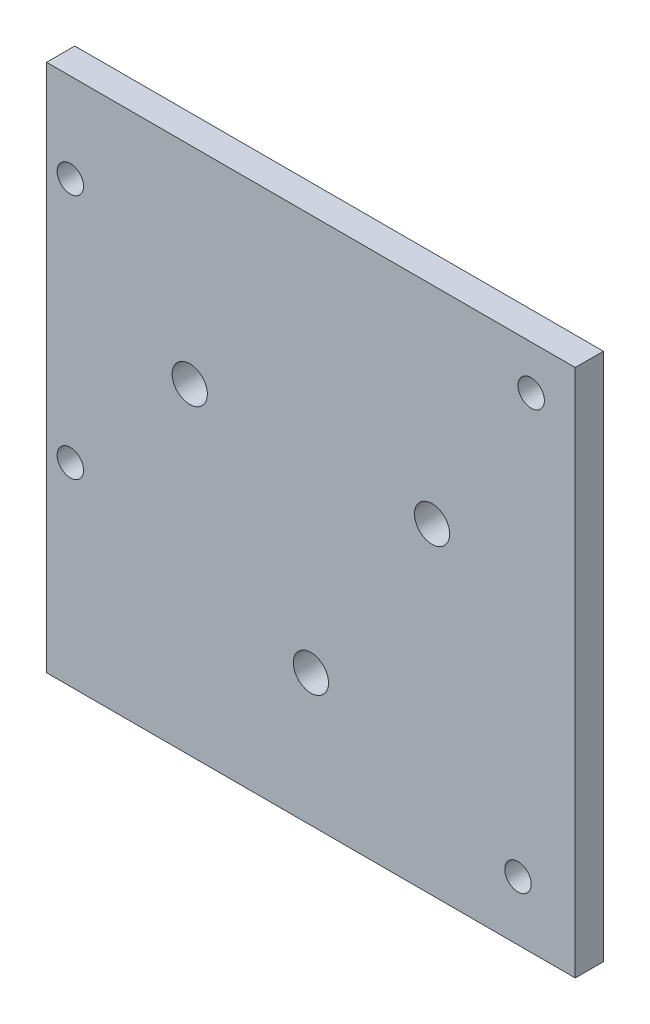
SolidWorks part; units mm, degrees
ref_plane "Front Plane" through (0, 0, 0) normal (0, 0, 1) x (1, 0, 0)
ref_plane "Top Plane" through (0, 0, 0) normal (0, 1, 0) x (1, 0, 0)
ref_plane "Right Plane" through (0, 0, 0) normal (1, 0, 0) x (0, 0, -1)
sketch "Sketch2" plane through (0, 0, 0) normal (0, 0, 1) x (1, 0, 0)
  line L1 (-32.5494, -8.3608) -> (27.4506, -8.3608)
  line L2 (-32.5494, -8.3608) -> (-32.5494, 51.6392)
  line L3 (-32.5494, 51.6392) -> (27.4506, 51.6392)
  line L4 (27.4506, -8.3608) -> (27.4506, 51.6392)
  dimension "D1" = 60
  dimension "D2" = 60
extrude "Boss-Extrude2" add sketch "Sketch2" along normal blind 3.2
sketch "Sketch3" plane through (0, 0, 3.2) normal (0, 0, 1) x (1, 0, 0)
  line L0 (22.4506, 46.6392) -> (22.4506, 1.9043) construction
  line L4 (27.4506, 51.6392) -> (-32.5494, 51.6392) construction
  line L6 (27.4506, -8.3608) -> (27.4506, 51.6392) construction
  circle A0 centre (20.9506, -1.6608) radius 1.5
  circle A1 centre (22.4506, 46.6392) radius 1.5
  circle A2 centre (-29.8494, 13.6392) radius 1.5
  circle A3 centre (-29.8494, 41.5392) radius 1.5
  dimension "D1" = 3
  dimension "D2" = 48.3
  dimension "D7" = 5
  dimension "D3" = 27.9
  dimension "D4" = 5.1
  dimension "D5" = 50.8
  dimension "D6" = 5
extrude "Arduino Holes" cut sketch "Sketch3" against normal blind 3.2
sketch "Sketch4" [suppressed] plane through (0, 0, 0) normal (0, 0, 1) x (1, 0, 0)
  line L1 (58.2904, -21.9623) -> (-1.7096, -21.9623)
  line L2 (58.2904, -21.9623) -> (58.2904, 8.0377)
  line L3 (58.2904, 8.0377) -> (-1.7096, 8.0377)
  line L4 (-1.7096, -21.9623) -> (-1.7096, 8.0377)
  dimension "D1" = 60
  dimension "D2" = 30
extrude "Boss-Extrude3" [suppressed] add sketch "Sketch4" along normal blind 3.2
sketch "Sketch5" plane through (0, 0, 0) normal (0, 0, -1) x (-1, 0, 0)
  line L0 (2.5494, -8.3608) -> (2.5494, 51.6392) construction
  line L1 (32.5494, -8.3608) -> (-27.4506, -8.3608) construction
  line L2 (-27.4506, 51.6392) -> (32.5494, 51.6392) construction
  circle A0 centre (2.5494, 6.6392) radius 2
  circle A1 centre (-11.2006, 28.1392) radius 2
  circle A2 centre (16.2994, 28.1392) radius 2
  point P12 (0, 0)
  dimension "D1" = 4
  dimension "D2" = 27.5
  dimension "D3" = 21.5
  dimension "D4" = 15
extrude "Cut-Extrude1" cut sketch "Sketch5" against normal blind 3.2
